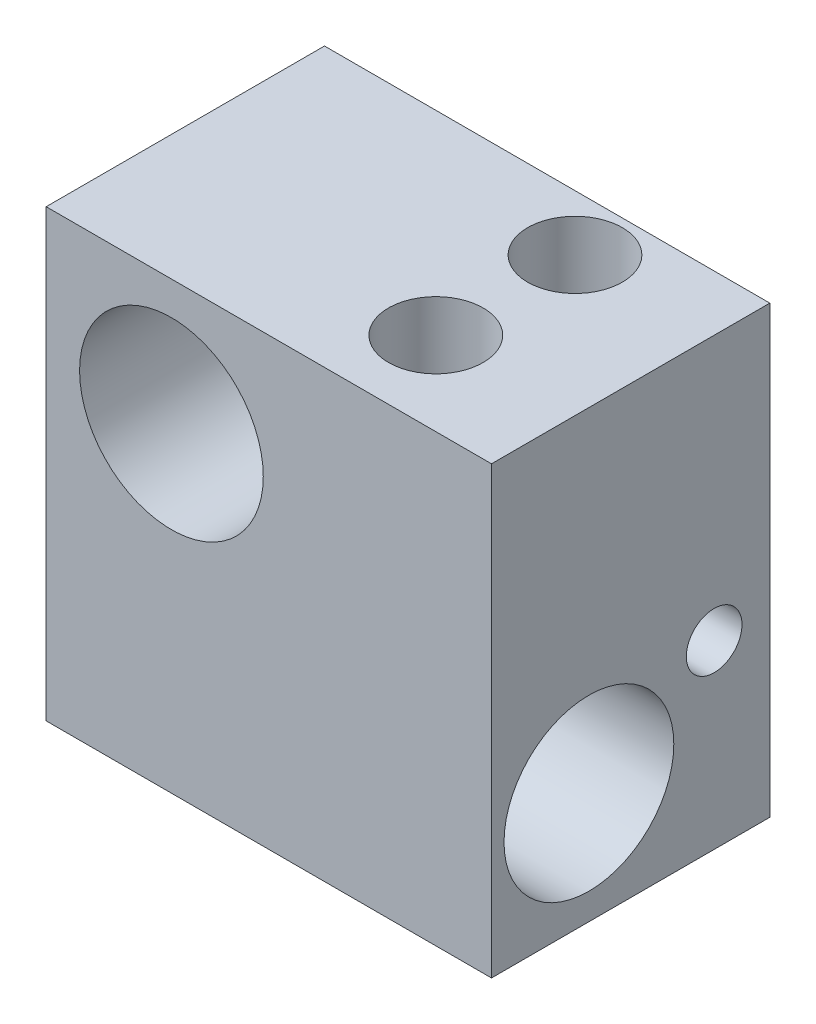
SolidWorks part; units mm, degrees
material "3.1325 (EN-AW 2017A)"
ref_plane "Plan de face" through (0, 0, 0) normal (0, 0, 1) x (1, 0, 0)
ref_plane "Plan de dessus" through (0, 0, 0) normal (0, 1, 0) x (1, 0, 0)
ref_plane "Plan de droite" through (0, 0, 0) normal (1, 0, 0) x (0, 0, -1)
sketch "Esquisse1" plane through (0, 0, 0) normal (0, 0, 1) x (1, 0, 0)
  line L1 (0, 0) -> (16, 0)
  line L2 (0, 0) -> (0, 16)
  line L3 (0, 16) -> (16, 16)
  line L4 (16, 0) -> (16, 16)
  dimension "D1" = 16
  dimension "D2" = 16
extrude "Boss.-Extru.1" add sketch "Esquisse1" along normal blind 10
sketch "Esquisse2" plane through (0, 0, 10) normal (0, 0, 1) x (1, 0, 0)
  line L0 (16, 16) -> (0, 16) construction
  line L2 (0, 16) -> (0, 0) construction
  circle A0 centre (4.5, 11.5) radius 3
  dimension "D1" = 6
  dimension "D2" = 4.5
  dimension "D3" = 4.5
hole_wizard "Dégagement M61" positions "Esquisse4" profile "Esquisse3" hole size "M6" standard "ISO" end condition through all
sketch "Esquisse4" plane through (0, 0, 10) normal (0, 0, 1) x (1, 0, 0)
  point P0 (4.5, 11.5)
sketch "Esquisse3" plane through (4.5, 11.5, 10) normal (1, 0, 0) x (0, -1, 0)
  line L0 (0, 0) -> (0, 10)
  line L1 (0, 10) -> (3.3, 10)
  line L2 (3.3, 10) -> (3.3, 0)
  line L5 (3.3, 0) -> (0, 0)
  line L11 (0, -6.35) -> (0, 107.95) construction
  dimension "Diamètre du perçage jusqu'au prochain" = 6.6
  dimension "Profondeur du perçage jusqu'au prochain" = 10
sketch "Esquisse5" plane through (16, 0, 0) normal (1, 0, 0) x (0, 0, -1)
  line L0 (-10, 0) -> (0, 0) construction
  line L1 (-10, 0) -> (-10, 16) construction
  line L2 (0, 0) -> (0, 16) construction
  circle A0 centre (-6.5, 4) radius 3
  circle A1 centre (-2, 6.5) radius 1.5
  dimension "D1" = 6
  dimension "D2" = 3
  dimension "D3" = 4
  dimension "D4" = 3.5
  dimension "D5" = 2
  dimension "D6" = 6.5
hole_wizard "Diamètre du perçage Ø6.1 (6.1)1" positions "Esquisse7" profile "Esquisse6" hole size "Ø6.1" standard "ISO" end condition through all
sketch "Esquisse7" plane through (16, 0, 0) normal (1, 0, 0) x (0, 0, -1)
  point P0 (-6.5, 4)
sketch "Esquisse6" plane through (16, 4, 6.5) normal (0, 1, 0) x (0, 0, -1)
  line L0 (0, 0) -> (0, 16)
  line L1 (0, 16) -> (3.05, 16)
  line L2 (3.05, 16) -> (3.05, 0)
  line L5 (3.05, 0) -> (0, 0)
  line L11 (0, -6.35) -> (0, 107.95) construction
  dimension "Diamètre du perçage jusqu'au prochain" = 6.1
  dimension "Profondeur du perçage jusqu'au prochain" = 16
hole_wizard "Diamètre du perçage Ø2.0 (2)1" positions "Esquisse9" profile "Esquisse8" hole size "Ø2.0" standard "ISO" end condition through all
sketch "Esquisse9" plane through (16, 0, 0) normal (1, 0, 0) x (0, 0, -1)
  point P0 (-2, 6.5)
sketch "Esquisse8" plane through (16, 6.5, 2) normal (0, 1, 0) x (0, 0, -1)
  line L0 (0, 0) -> (0, 16)
  line L1 (0, 16) -> (1, 16)
  line L2 (1, 16) -> (1, 0)
  line L5 (1, 0) -> (0, 0)
  line L11 (0, -6.35) -> (0, 107.95) construction
  dimension "Diamètre du perçage jusqu'au prochain" = 2
  dimension "Profondeur du perçage jusqu'au prochain" = 16
sketch "Esquisse10" plane through (0, 16, 0) normal (0, 1, 0) x (1, 0, 0)
  line L0 (16, -10) -> (16, 0) construction
  line L1 (16, -10) -> (0, -10) construction
  line L2 (16, 0) -> (0, 0) construction
  circle A0 centre (11, -7) radius 1.5
  circle A1 centre (11, -2) radius 1.5
  dimension "D1" = 3
  dimension "D2" = 3
  dimension "D3" = 5
  dimension "D4" = 5
  dimension "D5" = 3
  dimension "D6" = 2
hole_wizard "Dégagement M31" positions "Esquisse14" profile "Esquisse13" hole size "M3" standard "ISO"
sketch "Esquisse14" plane through (0, 16, 0) normal (0, 1, 0) x (1, 0, 0)
  point P0 (11, -7)
sketch "Esquisse13" plane through (11, 16, 7) normal (1, 0, 0) x (0, 0, 1)
  line L0 (0, 0) -> (0, 12.0215)
  line L1 (0, 12.0215) -> (1.7, 11)
  line L2 (1.7, 11) -> (1.7, 0)
  line L5 (1.7, 0) -> (0, 0)
  line L10 (0, 12.0215) -> (-1.7, 11) construction
  line L11 (0, -6.35) -> (0, 107.95) construction
  dimension "Diamètre du perçage" = 3.4
  dimension "Profondeur du perçage" = 11
  dimension "Angle de pointe" = 118
hole_wizard "Dégagement M32" positions "Esquisse16" profile "Esquisse15" hole size "M3" standard "ISO"
sketch "Esquisse16" plane through (0, 16, 0) normal (0, 1, 0) x (1, 0, 0)
  point P0 (11, -2)
sketch "Esquisse15" plane through (11, 16, 2) normal (1, 0, 0) x (0, 0, 1)
  line L0 (0, 0) -> (0, 10.0215)
  line L1 (0, 10.0215) -> (1.7, 9)
  line L2 (1.7, 9) -> (1.7, 0)
  line L5 (1.7, 0) -> (0, 0)
  line L10 (0, 10.0215) -> (-1.7, 9) construction
  line L11 (0, -6.35) -> (0, 107.95) construction
  dimension "Diamètre du perçage" = 3.4
  dimension "Profondeur du perçage" = 9
  dimension "Angle de pointe" = 118
chamfer "Chanfrein1" [suppressed] distance 0.25 angle 45
